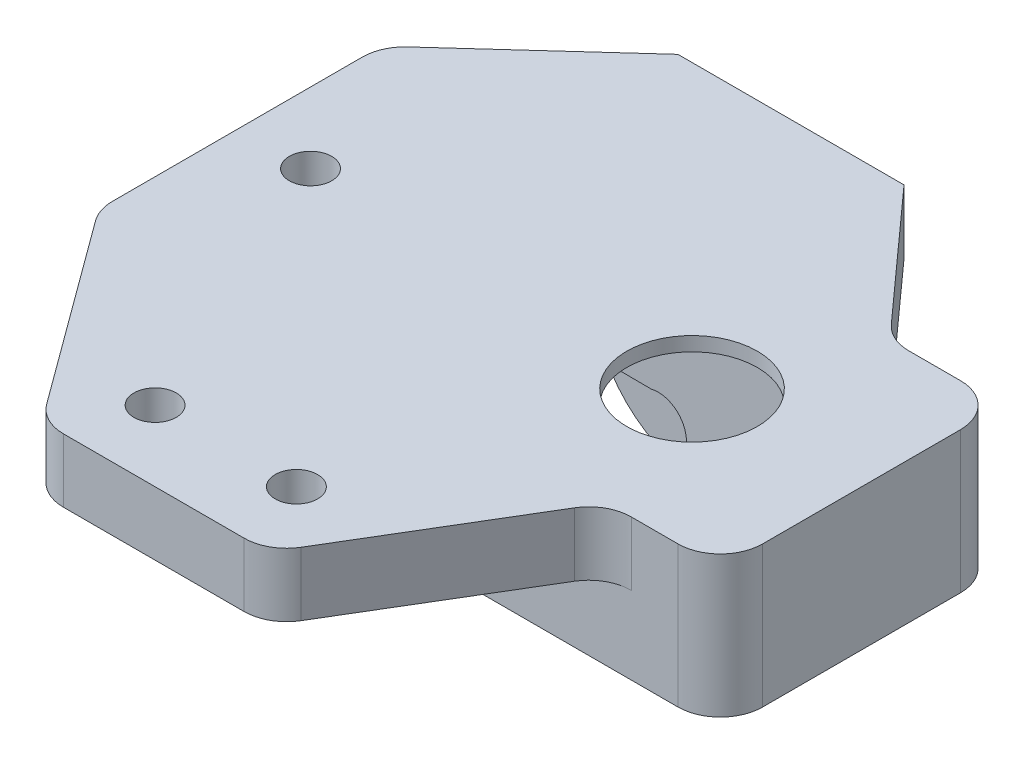
SolidWorks part; units mm, degrees
ref_plane "Front Plane" through (0, 0, 0) normal (0, 0, 1) x (1, 0, 0)
ref_plane "Top Plane" through (0, 0, 0) normal (0, 1, 0) x (1, 0, 0)
ref_plane "Right Plane" through (0, 0, 0) normal (1, 0, 0) x (0, 0, -1)
sketch "Sketch1" plane through (0, 0, 0) normal (0, 1, 0) x (1, 0, 0)
  line L0 (0, 0) -> (16, 0)
  line L1 (16, 0) -> (25, 15)
  line L2 (25, 15) -> (33, 15)
  line L3 (33, 15) -> (33, 35)
  line L4 (33, 35) -> (25, 35)
  line L5 (25, 35) -> (16, 45)
  line L6 (16, 45) -> (0, 45)
  line L7 (0, 45) -> (-11, 35)
  line L8 (-11, 35) -> (-11, 15)
  line L9 (-11, 15) -> (0, 0)
  dimension "D1" = 44
  dimension "D2" = 10
  dimension "D3" = 20
  dimension "D4" = 8
  dimension "D5" = 8
  dimension "D6" = 16
  dimension "D7" = 16
  dimension "D8" = 20
  dimension "D9" = 15
  dimension "D10" = 10
  dimension "D11" = 17
  dimension "D12" = 17
extrude "Boss-Extrude1" add sketch "Sketch1" along normal blind 4.5
sketch "Sketch2" plane through (0, 0, 0) normal (0, -1, 0) x (-1, 0, 0)
  line L1 (-33, 15) -> (1, 15)
  line L2 (-33, 15) -> (-33, 35)
  line L3 (-33, 35) -> (1, 35)
  line L4 (1, 15) -> (1, 35)
  dimension "D1" = 20
  dimension "D2" = 34
extrude "Boss-Extrude2" add sketch "Sketch2" along normal blind 5.5
sketch "Sketch3" plane through (0, -5.5, 0) normal (0, -1, 0) x (-1, 0, 0)
  line L0 (-33, 35) -> (-33, 15) construction
  circle A0 centre (-21, 25) radius 4.6217
  dimension "D1" = 25
  dimension "D2" = 12
extrude "Cut-Extrude1" cut sketch "Sketch3" against normal blind 15.5
sketch "Sketch4" plane through (0, -5.5, 0) normal (0, -1, 0) x (1, 0, 0)
  line L1 (4.6, -18.5) -> (27, -18.5)
  line L2 (4.6, -18.5) -> (4.6, -31.1)
  line L3 (4.6, -31.1) -> (27, -31.1)
  line L4 (27, -18.5) -> (27, -31.1)
  dimension "D1" = 22.4
  dimension "D2" = 12.6
  dimension "D3" = 18.5
  dimension "D4" = 4.6
extrude "Cut-Extrude2" cut sketch "Sketch4" against normal blind 9
sketch "Sketch5" plane through (0, 0, 0) normal (0, -1, 0) x (-1, 0, 0)
  circle A0 centre (-3, 5) radius 1.5
  circle A1 centre (-13, 5) radius 1.5
  dimension "D2" = 3
  dimension "D3" = 3
  dimension "D1" = 10
  dimension "D4" = 5
  dimension "D5" = 5
  dimension "D6" = 3
extrude "Cut-Extrude3" cut sketch "Sketch5" against normal blind 9
sketch "Sketch6" plane through (0, -5.5, 0) normal (0, -1, 0) x (-1, 0, 0)
  circle A0 centre (-2, 25) radius 1
  circle A1 centre (-30, 25) radius 1
  dimension "D3" = 2
  dimension "D4" = 2
  dimension "D1" = 25
  dimension "D2" = 25
  dimension "D5" = 30
  dimension "D6" = 2
extrude "Cut-Extrude4" cut sketch "Sketch6" against normal blind 9
sketch "Sketch7" plane through (0, 0, 0) normal (0, -1, 0) x (-1, 0, 0)
  circle A0 centre (6, 25) radius 1.5
  circle A1 centre (-21, 25) radius 4.6217 construction
  dimension "D1" = 3
  dimension "D2" = 27
  dimension "D3" = 25
extrude "Cut-Extrude5" cut sketch "Sketch7" against normal blind 19
sketch "Sketch8" plane through (0, 0, 0) normal (0, -1, 0) x (-1, 0, 0)
  line L1 (0, 44) -> (-16, 44)
  line L2 (0, 44) -> (0, 39)
  line L3 (0, 39) -> (-16, 39)
  line L4 (-16, 44) -> (-16, 39)
  dimension "D1" = 5
  dimension "D2" = 16
  dimension "D3" = 39
extrude "Boss-Extrude3" add sketch "Sketch8" along normal blind 15
sketch "Sketch9" plane through (0, 0, -45) normal (0, 0, -1) x (-1, 0, 0)
  circle A1 centre (-12.5, -5) radius 0.75
  circle A2 centre (-3.5, -5) radius 0.75
  dimension "D6" = 1.5
  dimension "D7" = 1.5
  dimension "D1" = 9
  dimension "D2" = 3.5
extrude "Cut-Extrude6" cut sketch "Sketch9" against normal blind 6
sketch "Sketch10" plane through (0, 0, -45) normal (0, 0, -1) x (-1, 0, 0)
  circle A0 centre (-8, -5) radius 2
  dimension "D3" = 4
  dimension "D1" = 8
  dimension "D2" = 5
extrude "Cut-Extrude7" cut sketch "Sketch10" against normal blind 36
fillet "Fillet1" radius 3 10 edges at (-11, 2.25, -35) (25, 2.25, -35) (33, -0.5, -35) (33, -0.5, -15) (25, 2.25, -15) (-11, 2.25, -15) (16, 2.25, 0) (0, 2.25, 0) (-1, -2.75, -35) (-1, -2.75, -15)
fillet "Fillet2" radius 8 2 edges at (16, -15, -41.5) (0, -15, -41.5)
fillet "Fillet3" radius 2 1 edges at (8, 0, -39)
sketch "Sketch11" plane through (0, 0, -39) normal (0, 0, 1) x (1, 0, 0)
  line L0 (3.5, -3) -> (12.0149, -3.0597)
  line L1 (3.5, -7) -> (12.0149, -6.9403)
  arc A0 (12.0149, -6.9403) -> (12.0149, -3.0597) centre (12.5, -5) ccw
  arc A1 (3.5, -3) -> (3.5, -7) centre (3.5, -5) ccw
  dimension "D1" = 4
  dimension "D2" = 4
extrude "Cut-Extrude8" cut sketch "Sketch11" along normal blind 30
ref_plane "Plane1" through (8, 0, 0) normal (1, 0, 0) x (0, 0, -1)
ref_plane "Plane2" through (0, -5, 0) normal (0, 1, 0) x (1, 0, 0)
ref_axis "Axis1" through (8, -5, -47.25) along (0, 0, 1)
ref_axis "Axis2" through (3, 4.5, -5) along (0, -1, 0)
ref_axis "Axis3" through (13, 4.5, -5) along (0, -1, 0)
ref_axis "Axis4" through (-6, 4.5, -25) along (0, -1, 0)
ref_plane "Plane3" through (21, 0, 0) normal (1, 0, 0) x (0, 0, -1)
ref_plane "Plane4" through (0, 0, -25) normal (0, 0, 1) x (1, 0, 0)
ref_axis "Axis5" through (21, -15.975, -25) along (0, 1, 0)
